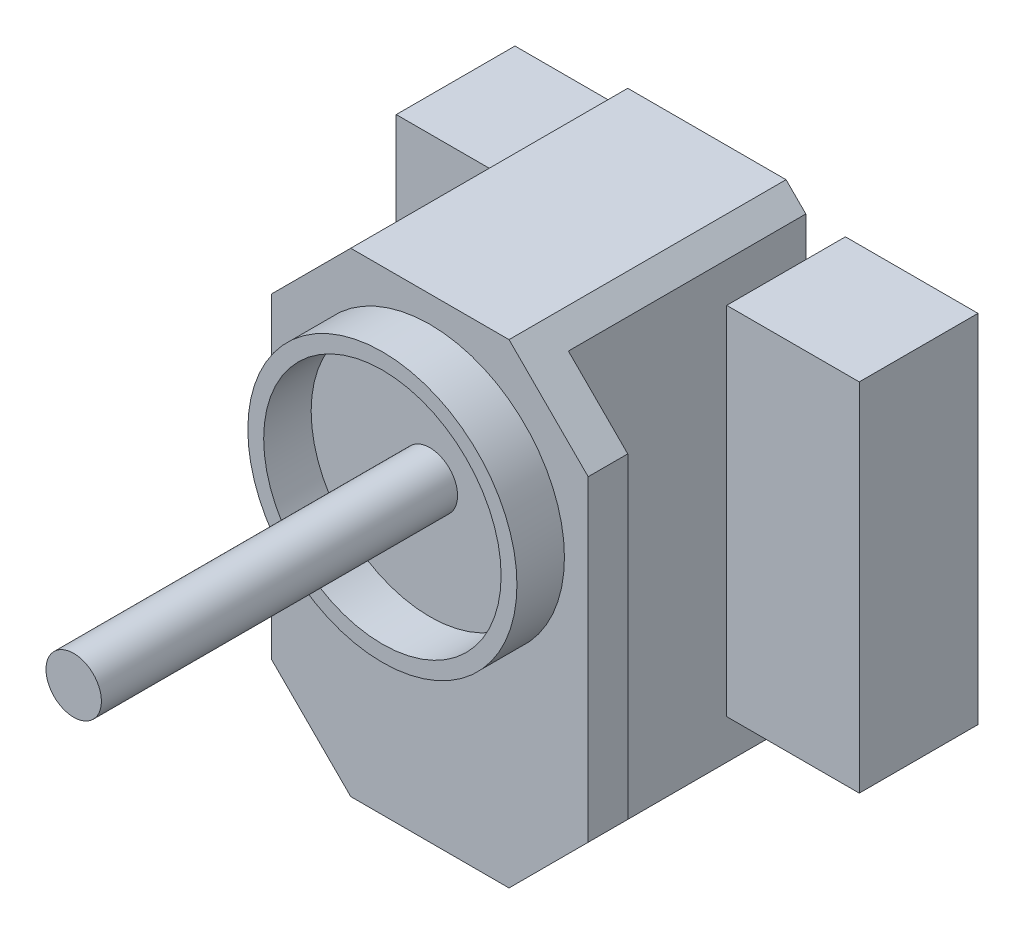
SolidWorks part; units mm, degrees
material "ABS"
ref_plane "前基準面" through (0, 0, 0) normal (0, 0, 1) x (1, 0, 0)
ref_plane "上基準面" through (0, 0, 0) normal (0, 1, 0) x (1, 0, 0)
ref_plane "右基準面" through (0, 0, 0) normal (1, 0, 0) x (0, 0, -1)
sketch "草圖1" plane through (0, 0, 0) normal (0, 0, 1) x (1, 0, 0)
  line L1 (-12.5, -30) -> (12.5, -30)
  line L2 (-12.5, -30) -> (-12.5, 30)
  line L3 (-12.5, 30) -> (12.5, 30)
  line L4 (12.5, -30) -> (12.5, 30)
  line L5 (-12.5, -30) -> (12.5, 30) construction
  line L6 (-12.5, 30) -> (12.5, -30) construction
  point P0 (0, 0)
  dimension "D1" = 60
  dimension "D2" = 25
extrude "填料-伸長1" add sketch "草圖1" along normal blind 35
sketch "草圖2" plane through (0, 0, 0) normal (0, 0, -1) x (-1, 0, 0)
  line L1 (-10, 20.25) -> (10, 20.25)
  line L2 (-10, 20.25) -> (-10, -20.25)
  line L3 (-10, -20.25) -> (10, -20.25)
  line L4 (10, 20.25) -> (10, -20.25)
  line L5 (-10, 20.25) -> (10, -20.25) construction
  line L6 (-10, -20.25) -> (10, 20.25) construction
  point P0 (0, 0)
  dimension "D1" = 20
  dimension "D2" = 40.5
extrude "除料-伸長1" cut sketch "草圖2" against normal blind 31.5
sketch "草圖5" plane through (0, 0, 35) normal (0, 0, 1) x (1, 0, 0)
  line L1 (-20, -30) -> (20, -30)
  line L2 (-20, -30) -> (-20, 30)
  line L3 (-20, 30) -> (20, 30)
  line L4 (20, -30) -> (20, 30)
  line L5 (-20, -30) -> (20, 30) construction
  line L6 (-20, 30) -> (20, -30) construction
  point P0 (0, 0)
  dimension "D1" = 40
  dimension "D2" = 60
extrude "填料-伸長4" add sketch "草圖5" against normal blind 5
sketch "草圖6" plane through (0, 0, 0) normal (0, 0, -1) x (-1, 0, 0)
  line L1 (-5, 24.75) -> (5, 24.75) construction
  line L2 (-5, 24.75) -> (-5, -24.75) construction
  line L3 (-5, -24.75) -> (5, -24.75) construction
  line L4 (5, 24.75) -> (5, -24.75) construction
  line L5 (-5, 24.75) -> (5, -24.75) construction
  line L6 (-5, -24.75) -> (5, 24.75) construction
  circle A0 centre (5, 24.75) radius 1.65
  circle A2 centre (-5, 24.75) radius 1.65
  circle A3 centre (-5, -24.75) radius 1.65
  circle A4 centre (5, -24.75) radius 1.65
  point P4 (0, 0)
  dimension "D1" = 24.75
  dimension "D2" = 3.3
  dimension "D3" = 10
  dimension "D4" = 2
  dimension "D5" = 2
extrude "除料-伸長2" cut sketch "草圖6" against normal blind 6
sketch "草圖10" plane through (-12.5, 0, 0) normal (-1, 0, 0) x (0, 0, 1)
  line L0 (0, 30) -> (0, -30) construction
  line L1 (-5, -22.5) -> (10, -22.5)
  line L2 (-5, -22.5) -> (-5, 22.5)
  line L3 (-5, 22.5) -> (10, 22.5)
  line L4 (10, -22.5) -> (10, 22.5)
  point P6 (0, 0)
  point P7 (-5, 0)
  dimension "D1" = 15
  dimension "D2" = 45
  dimension "D3" = 5
extrude "填料-伸長7" add sketch "草圖10" along normal blind 16.75
sketch "草圖18" plane through (0, 0, -5) normal (0, 0, -1) x (-1, 0, 0)
  line L0 (12.5, 22.5) -> (12.5, -22.5) construction
  line L1 (29.25, -22.5) -> (12.5, -22.5) construction
  line L2 (29.25, 22.5) -> (12.5, 22.5) construction
  circle A0 centre (16, -20) radius 1.25
  circle A1 centre (16, 20) radius 1.25
  dimension "D1" = 2.5
  dimension "D2" = 2.5
  dimension "D6" = 2.5
  dimension "D3" = 3.5
  dimension "D4" = 3.5
  dimension "D5" = 2.5
extrude "除料-伸長4" cut sketch "草圖18" against normal blind 5
sketch "草圖17" plane through (0, 0, 0) normal (0, 0, -1) x (-1, 0, 0)
  line L0 (29.25, 22.5) -> (29.25, -22.5) construction
  circle A0 centre (24.25, 0) radius 1.65
  circle A1 centre (24.25, -15) radius 1.65
  circle A2 centre (24.25, 15) radius 1.65
  dimension "D2" = 3.3
  dimension "D3" = 3.3
  dimension "D5" = 3.3
  dimension "D1" = 15
  dimension "D4" = 15
  dimension "D6" = 5
extrude "除料-伸長3" cut sketch "草圖17" against normal blind 4 and the other way blind 8
mirror "鏡射1" about plane through (0, 0, 0) normal (1, 0, 0) of "除料-伸長4", "填料-伸長7", "除料-伸長3"
sketch "草圖13" plane through (0, 0, 35) normal (0, 0, 1) x (1, 0, 0)
  circle A0 centre (0, 9.675) radius 3.5
  point P0 (0, 9.675)
  dimension "D1" = 7
extrude "填料-伸長10" add sketch "草圖13" along normal blind 45
sketch "草圖15" plane through (0, 0, 35) normal (0, 0, 1) x (1, 0, 0)
  circle A0 centre (0, 9.675) radius 15
  circle A1 centre (0, 9.675) radius 17
  dimension "D1" = 30
  dimension "D2" = 34
extrude "填料-伸長11" add sketch "草圖15" along normal blind 6
chamfer "導角3" distance 10 angle 45 4 edges at (20, 30, 32.5) (-20, 30, 32.5) (20, -30, 32.5) (-20, -30, 32.5)
